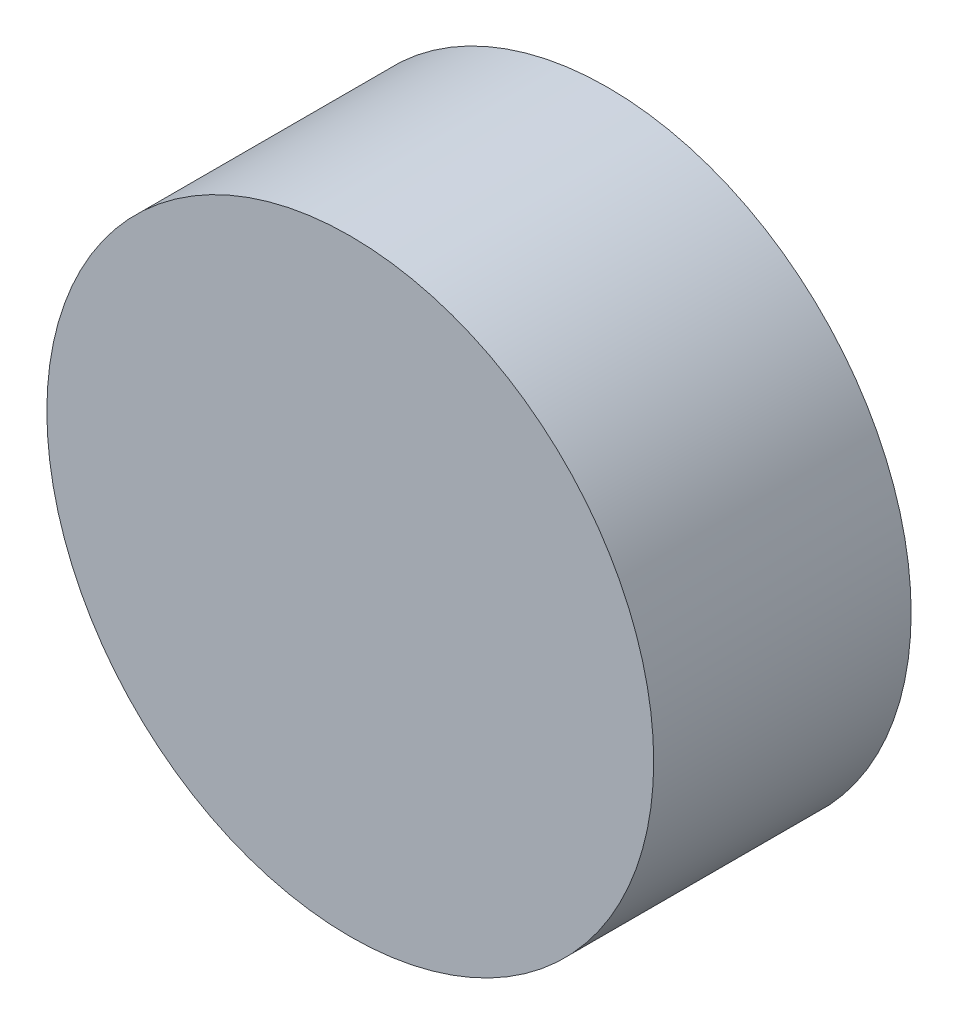
SolidWorks part; units mm, degrees
ref_plane "Ebene vorne" through (0, 0, 0) normal (0, 0, 1) x (1, 0, 0)
ref_plane "Ebene oben" through (0, 0, 0) normal (0, 1, 0) x (1, 0, 0)
ref_plane "Ebene rechts" through (0, 0, 0) normal (1, 0, 0) x (0, 0, -1)
sketch "Skizze1" plane through (0, 0, 0) normal (0, 0, 1) x (1, 0, 0)
  circle A0 centre (0, -12) radius 25.9305
  arc A1 (-18.2154, 1.9286) -> (-20.3588, -1.4487) centre (0, -12) ccw construction
  circle A5 centre (0, -12) radius 22.9305
  arc A6 (-21.1071, -3.039) -> (-22.3431, -6.8432) centre (0, -12) ccw construction
  dimension "D1" = 3
extrude "Aufsatz-Linear austragen1" add sketch "Skizze1" along normal blind 3 and the other way up to surface (19 mm away)
sketch "Skizze3" plane through (0, 0, 3) normal (0, 0, 1) x (1, 0, 0)
  circle A0 centre (0, -12) radius 25.9305
  circle A1 centre (0, -12) radius 25.9305 construction
sketch "Skizze4" plane through (0, 0, -4) normal (0, 0, 1) x (1, 0, 0)
  circle A0 centre (0, -12) radius 16.2
  circle A1 centre (0, -12) radius 16.2 construction
extrude "Aufsatz-Linear austragen5" add sketch "Skizze3" against normal up to surface (3 mm away)
extrude "Aufsatz-Linear austragen6" add sketch "Skizze4" along normal up to surface (7 mm away) contours A0 up to face at (25.9305, -12, 3)
sketch "Skizze5" plane through (0, 0, -4) normal (0, 0, -1) x (-1, 0, 0)
  circle A0 centre (0, -12) radius 5
  circle A1 centre (0, -12) radius 16.2 construction
  dimension "D1" = 10
extrude "Aufsatz-Linear austragen7" add sketch "Skizze5" along normal blind 3
sketch "Skizze6" plane through (0, 0, -7) normal (0, 0, -1) x (-1, 0, 0)
  circle A0 centre (0, -12) radius 1.8
  circle A1 centre (0, -12) radius 5 construction
  dimension "D1" = 3.6
extrude "Schnitt-Linear austragen1" cut sketch "Skizze6" against normal blind 4
chamfer "Fase1" distance 3 angle 30 1 edges at (-5, -12, -7)
sketch "Skizze7" plane through (0, 0, -19) normal (0, 0, -1) x (-1, 0, 0)
  arc A0 (2.5053, 7.8313) -> (2, 10.8431) centre (8.0643, 10.3122) cw
  arc A1 (2, 10.8431) -> (2.5, 7.8431) centre (8.0643, 10.3122) ccw construction
  arc A2 (2.5133, 7.8415) -> (3.7437, 10.6229) centre (-2.2621, 11.6167) ccw construction
  arc A3 (2.5053, 7.8313) -> (3.7437, 10.6229) centre (-2.2621, 11.6167) ccw
  arc A4 (7.3584, 6.5852) -> (7.618, 9.6281) centre (13.3598, 7.6057) cw
  circle A5 centre (0, -12) radius 22.9305 construction
  arc A6 (2, 10.8431) -> (3.7437, 10.6229) centre (0, -12) cw
  circle A7 centre (0, -12) radius 22.9305 construction
  arc A8 (7.3584, 6.5852) -> (9.2522, 8.9811) centre (3.6822, 11.4373) ccw
  arc A9 (7.618, 9.6281) -> (9.2522, 8.9811) centre (0, -12) cw
  arc A10 (11.7492, 4.1714) -> (12.7574, 7.0541) centre (17.8158, 3.6673) cw
  arc A11 (11.7492, 4.1714) -> (14.1793, 6.021) centre (9.3951, 9.7853) ccw
  arc A12 (12.7574, 7.0541) -> (14.1793, 6.021) centre (0, -12) cw
  arc A13 (15.4017, 0.7414) -> (17.0951, 3.2828) centre (21.1524, -1.2555) cw
  arc A14 (15.4017, 0.7414) -> (18.2154, 1.9286) centre (14.5177, 6.7644) ccw
  arc A15 (17.0951, 3.2828) -> (18.2154, 1.9286) centre (0, -12) cw
  arc A16 (18.0865, -3.4891) -> (20.3588, -1.4487) centre (23.1599, -6.8534) cw
  arc A17 (18.0865, -3.4891) -> (21.1071, -3.039) centre (18.7281, 2.5644) ccw
  arc A18 (20.3588, -1.4487) -> (21.1071, -3.039) centre (0, -12) cw
  arc A19 (19.6348, -8.2545) -> (22.3431, -6.8432) centre (23.7122, -12.7748) cw
  arc A20 (19.6348, -8.2545) -> (22.6725, -8.5696) centre (21.7618, -2.5506) ccw
  arc A21 (22.3431, -6.8432) -> (22.6725, -8.5696) centre (0, -12) cw
  arc A22 (19.9495, -13.2551) -> (22.9236, -12.5617) centre (22.7745, -18.6474) cw
  arc A23 (19.9495, -13.2551) -> (22.8133, -14.3158) centre (23.4281, -8.2594) ccw
  arc A24 (22.9236, -12.5617) -> (22.8133, -14.3158) centre (0, -12) cw
  arc A25 (19.0106, -18.1769) -> (22.0638, -18.245) centre (20.4059, -24.1023) cw
  arc A26 (19.0106, -18.1769) -> (21.5206, -19.9165) centre (23.6223, -14.2033) ccw
  arc A27 (22.0638, -18.245) -> (21.5206, -19.9165) centre (0, -12) cw
  arc A28 (16.8772, -22.7106) -> (19.8175, -23.5358) centre (16.7551, -28.7969) cw
  arc A29 (16.8772, -22.7106) -> (18.8758, -25.0197) centre (22.3322, -20.0087) ccw
  arc A30 (19.8175, -23.5358) -> (18.8758, -25.0197) centre (0, -12) cw
  arc A31 (13.6833, -26.5713) -> (16.3261, -28.1018) centre (12.0515, -32.436) cw
  arc A32 (13.6833, -26.5713) -> (15.0449, -29.3049) centre (19.6389, -25.3109) ccw
  arc A33 (16.3261, -28.1018) -> (15.0449, -29.3049) centre (0, -12) cw
  arc A34 (9.6297, -29.5164) -> (11.8088, -31.6561) centre (6.5906, -34.791) cw
  arc A35 (9.6297, -29.5164) -> (10.2687, -32.5028) centre (15.7117, -29.7767) ccw
  arc A36 (11.8088, -31.6561) -> (10.2687, -32.5028) centre (0, -12) cw
  arc A37 (4.971, -31.3609) -> (6.5496, -33.9753) centre (0.7157, -35.714) cw
  arc A38 (4.971, -31.3609) -> (4.8472, -34.4123) centre (10.7972, -33.1255) ccw
  arc A39 (6.5496, -33.9753) -> (4.8472, -34.4123) centre (0, -12) cw
  arc A40 (0, -31.9889) -> (0.8788, -34.9137) centre (-5.2042, -35.147) cw
  arc A41 (0, -31.9889) -> (-0.8788, -34.9137) centre (5.2042, -35.147) ccw
  arc A42 (0.8788, -34.9137) -> (-0.8788, -34.9137) centre (0, -12) cw
  arc A43 (-4.971, -31.3609) -> (-4.8472, -34.4123) centre (-10.7972, -33.1255) cw
  arc A44 (-4.971, -31.3609) -> (-6.5496, -33.9753) centre (-0.7157, -35.714) ccw
  arc A45 (-4.8472, -34.4123) -> (-6.5496, -33.9753) centre (0, -12) cw
  arc A46 (-9.6297, -29.5164) -> (-10.2687, -32.5028) centre (-15.7117, -29.7767) cw
  arc A47 (-9.6297, -29.5164) -> (-11.8088, -31.6561) centre (-6.5906, -34.791) ccw
  arc A48 (-10.2687, -32.5028) -> (-11.8088, -31.6561) centre (0, -12) cw
  arc A49 (-13.6833, -26.5713) -> (-15.0449, -29.3049) centre (-19.6389, -25.3109) cw
  arc A50 (-13.6833, -26.5713) -> (-16.3261, -28.1018) centre (-12.0515, -32.436) ccw
  arc A51 (-15.0449, -29.3049) -> (-16.3261, -28.1018) centre (0, -12) cw
  arc A52 (-16.8772, -22.7106) -> (-18.8758, -25.0197) centre (-22.3322, -20.0087) cw
  arc A53 (-16.8772, -22.7106) -> (-19.8175, -23.5358) centre (-16.7551, -28.7969) ccw
  arc A54 (-18.8758, -25.0197) -> (-19.8175, -23.5358) centre (0, -12) cw
  arc A55 (-19.0106, -18.1769) -> (-21.5206, -19.9165) centre (-23.6223, -14.2033) cw
  arc A56 (-19.0106, -18.1769) -> (-22.0638, -18.245) centre (-20.4059, -24.1023) ccw
  arc A57 (-21.5206, -19.9165) -> (-22.0638, -18.245) centre (0, -12) cw
  arc A58 (-19.9495, -13.2551) -> (-22.8133, -14.3158) centre (-23.4281, -8.2594) cw
  arc A59 (-19.9495, -13.2551) -> (-22.9236, -12.5617) centre (-22.7745, -18.6474) ccw
  arc A60 (-22.8133, -14.3158) -> (-22.9236, -12.5617) centre (0, -12) cw
  arc A61 (-19.6348, -8.2545) -> (-22.6725, -8.5696) centre (-21.7618, -2.5506) cw
  arc A62 (-19.6348, -8.2545) -> (-22.3431, -6.8432) centre (-23.7122, -12.7748) ccw
  arc A63 (-22.6725, -8.5696) -> (-22.3431, -6.8432) centre (0, -12) cw
  arc A64 (-18.0865, -3.4891) -> (-21.1071, -3.039) centre (-18.7281, 2.5644) cw
  arc A65 (-18.0865, -3.4891) -> (-20.3588, -1.4487) centre (-23.1599, -6.8534) ccw
  arc A66 (-21.1071, -3.039) -> (-20.3588, -1.4487) centre (0, -12) cw
  arc A67 (-15.4017, 0.7414) -> (-18.2154, 1.9286) centre (-14.5177, 6.7644) cw
  arc A68 (-15.4017, 0.7414) -> (-17.0951, 3.2828) centre (-21.1524, -1.2555) ccw
  arc A69 (-18.2154, 1.9286) -> (-17.0951, 3.2828) centre (0, -12) cw
  arc A70 (-11.7492, 4.1714) -> (-14.1793, 6.021) centre (-9.3951, 9.7853) cw
  arc A71 (-11.7492, 4.1714) -> (-12.7574, 7.0541) centre (-17.8158, 3.6673) ccw
  arc A72 (-14.1793, 6.021) -> (-12.7574, 7.0541) centre (0, -12) cw
  arc A73 (-7.3584, 6.5852) -> (-9.2522, 8.9811) centre (-3.6822, 11.4373) cw
  arc A74 (-7.3584, 6.5852) -> (-7.618, 9.6281) centre (-13.3598, 7.6057) ccw
  arc A75 (-9.2522, 8.9811) -> (-7.618, 9.6281) centre (0, -12) cw
  arc A76 (-2.5053, 7.8313) -> (-3.7437, 10.6229) centre (2.2621, 11.6167) cw
  arc A77 (-2.5053, 7.8313) -> (-2, 10.8431) centre (-8.0643, 10.3122) ccw
  arc A78 (-3.7437, 10.6229) -> (-2, 10.8431) centre (0, -12) cw
  point P139 (0, -12)
  dimension "D1" = 25
extrude "Aufsatz-Linear austragen9" add sketch "Skizze7" against normal through all
sketch "Skizze8" plane through (0, 0, -7.5) normal (0, 0, -1) x (-1, 0, 0)
  circle A1 centre (0, -12) radius 22.9305
  arc A2 (-22.6725, -8.5696) -> (-22.9236, -12.5617) centre (0, -12) ccw construction
  circle A5 centre (0, -12.0353) radius 19.8767
  circle A6 centre (0, -12.0353) radius 19.8767 construction
extrude "Aufsatz-Linear austragen10" add sketch "Skizze8" along normal up to surface (4 mm away)
